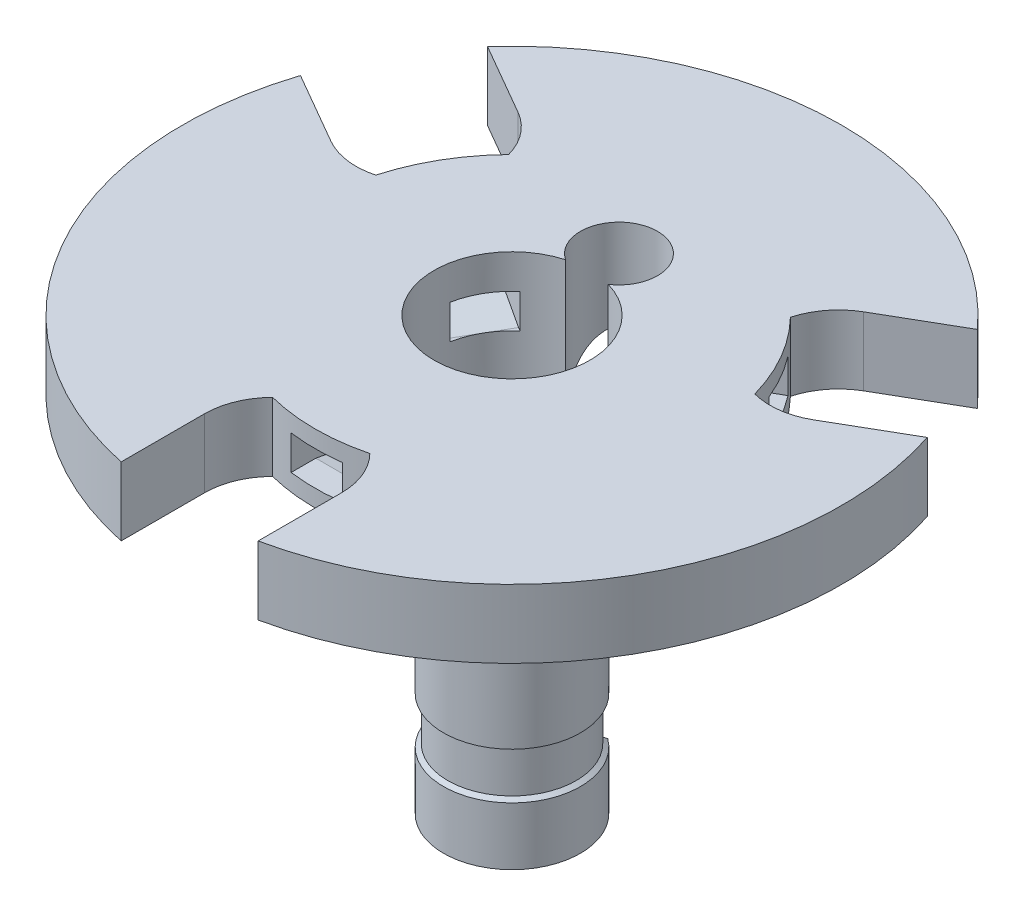
SolidWorks part; units mm, degrees
note: The reader was unsure of these and kept them because the rebuilt part matched: shared geometry of "Sketch1<4>".
ref_plane "Front Plane" through (0, 0, 0) normal (0, 0, 1) x (1, 0, 0)
ref_plane "Top Plane" through (0, 0, 0) normal (0, 1, 0) x (1, 0, 0)
ref_plane "Right Plane" through (0, 0, 0) normal (1, 0, 0) x (0, 0, -1)
sketch "Sketch1" plane through (0, 0, 0) normal (0, 1, 0) x (1, 0, 0)
  line L0 (-2, -16.5) -> (-2, -13.96)
  line L1 (2, -16.5) -> (2, -13.96)
  line L2 (0, -16.5) -> (0, 0) construction
  line L3 (0, 0) -> (38.1669, 22.0357) construction
  line L4 (0, 0) -> (-43.0695, 24.8662) construction
  line L5 (-11.0897, 8.7121) -> (-13.0897, 5.2479) construction
  line L6 (-13.2894, 9.9821) -> (-15.2894, 6.5179) construction
  line L7 (11.0897, 8.7121) -> (13.0897, 5.2479) construction
  line L8 (13.2894, 9.9821) -> (15.2894, 6.5179) construction
  line L9 (13.0897, 5.2479) -> (15.2894, 6.5179)
  line L10 (13.2894, 9.9821) -> (11.0897, 8.7121)
  line L11 (-15.2894, 6.5179) -> (-13.0897, 5.2479)
  line L12 (-13.2894, 9.9821) -> (-11.0897, 8.7121)
  line L13 (-4, -16.5) -> (-4, -13.96)
  line L14 (4, -16.5) -> (4, -13.96)
  line L15 (-16.2894, 4.7859) -> (-14.0897, 3.5159)
  line L16 (-12.2894, 11.7141) -> (-10.0897, 10.4441)
  line L17 (12.2894, 11.7141) -> (10.0897, 10.4441)
  line L18 (14.0897, 3.5159) -> (16.2894, 4.7859)
  line L19 (4, -16.5) -> (2.3, -16.5)
  line L20 (-4, -16.5) -> (-2.3, -16.5)
  line L21 (16.2894, 4.7859) -> (15.4394, 6.2581)
  line L22 (12.2894, 11.7141) -> (13.1394, 10.2419)
  line L23 (-12.2894, 11.7141) -> (-13.1394, 10.2419)
  line L24 (-16.2894, 4.7859) -> (-15.4394, 6.2581)
  line L25 (4, -16.5) -> (4, -18.8298)
  line L26 (-4, -16.5) -> (-4, -18.8298)
  line L27 (16.2894, 4.7859) -> (18.3071, 5.9508)
  line L28 (12.2894, 11.7141) -> (14.3071, 12.879)
  line L29 (-12.2894, 11.7141) -> (-14.3071, 12.879)
  line L30 (-16.2894, 4.7859) -> (-18.3071, 5.9508)
  circle A0 centre (0, 0) radius 16.5
  circle A1 centre (0, 0) radius 19.25
  arc A2 (-1.9963, -16.3788) -> (1.9963, -16.3788) centre (0, -16.5) ccw
  arc A3 (2, -13.96) -> (-2, -13.96) centre (0, -13.96) ccw
  circle A4 centre (0, 0) radius 4
  arc A5 (15.1826, 6.4605) -> (13.1863, 9.9183) centre (14.2894, 8.25) ccw
  arc A6 (-13.1863, 9.9183) -> (-15.1826, 6.4605) centre (-14.2894, 8.25) ccw
  arc A7 (-13.0897, 5.2479) -> (-11.095, 8.7151) centre (-12.0897, 6.98) ccw
  arc A8 (11.0897, 8.7121) -> (13.0897, 5.2479) centre (12.0897, 6.98) ccw
  arc A9 (4, -13.96) -> (-4, -13.96) centre (0, -13.96) ccw
  arc A10 (-14.0897, 3.5159) -> (-10.1003, 10.4502) centre (-12.0897, 6.98) ccw
  arc A11 (10.0897, 10.4441) -> (14.0897, 3.5159) centre (12.0897, 6.98) ccw
  arc A12 (-2.3, -16.5) -> (2.3, -16.5) centre (0, -16.5) ccw
  arc A13 (-2.2958, -16.3606) -> (2.2958, -16.3606) centre (0, -16.5) ccw construction
  arc A14 (-13.1394, 10.2419) -> (-15.4394, 6.2581) centre (-14.2894, 8.25) ccw
  arc A15 (15.4394, 6.2581) -> (13.1394, 10.2419) centre (14.2894, 8.25) ccw
  arc A16 (15.3166, 6.1921) -> (13.0208, 10.1685) centre (14.2894, 8.25) ccw construction
  arc A17 (-13.0208, 10.1685) -> (-15.3166, 6.1921) centre (-14.2894, 8.25) ccw construction
  circle A18 centre (0, 0) radius 11.5
  dimension "D1" = 38.5
  dimension "D2" = 33
  dimension "D3" = 4
  dimension "D5" = 8
  dimension "D8" = 4
  dimension "D9" = 4
  dimension "D10" = 4
  dimension "D11" = 4
  dimension "D20" = 23
  dimension "D4" = 2.54
  dimension "D6" = 120
  dimension "D7" = 120
  dimension "D12" = 2.54
  dimension "D13" = 2
  dimension "D14" = 2
  dimension "D15" = 2.54
  dimension "D16" = 2
  dimension "D17" = 2
  dimension "D18" = 0.3
  dimension "D19" = 0.3
extrude "Boss-Extrude1" add sketch "Sketch1" against normal blind 4 contours A1 A6 L12 A0 L10 A5 L9 L1 A2 L0 L11 | A11 L17 A0 L16 A10 L15 L13 A9 L14 L18 A4 | A18 A11 L17 A0 L16 A10 | A18 A9 L14 A0 L18 A11 | A18 A10 L15 A0 L13 A9 | A9 A18 | A10 A18 | A11 A18 | L30 A1 L26 L13 A0 L15 | L28 A1 L29 L16 A0 L17
extrude "Boss-Extrude2" add sketch "Sketch1<4>" against normal offset from surface (27.15 mm away) 27.15 contours A4 up to face at (0, 0, 0)
sketch "Sketch1<4>" plane through (0, 0, 0) normal (0, 1, 0) x (1, 0, 0) same geometry as "Sketch1"
sketch "Sketch2" plane through (0, 0, 0) normal (1, 0, 0) x (0, 0, -1)
  line L0 (0, 0) -> (0, -27.15) construction
  line L2 (2.3, -27.15) -> (2.3, -25.15)
  line L3 (2.5, 0) -> (2.3, -25.15)
  line L4 (-4, -27.15) -> (4, -27.15) construction
  line L6 (19.25, 0) -> (-19.25, 0) construction
  line L7 (0, 0) -> (2.5, 0)
  line L8 (0, -27.15) -> (2.3, -27.15)
  line L9 (0, 0) -> (0, -27.15)
  line L10 (0, -27.15) -> (2.3, -27.15)
  dimension "D1" = 2
  dimension "D2" = 2.5
  dimension "D3" = 2.3
revolve "Cut-Revolve4" cut sketch "Sketch2" angle 360 about L0
fillet "Fillet3" radius 10 1 edges at (0, -4, 4)
ref_axis "Axis1" through (0, 0, 0) along (0, -1, 0)
sketch "Sketch5" plane through (0, 0, 0) normal (0, 0, 1) x (1, 0, 0)
  line L0 (0, 0) -> (0, -7) construction
  line L1 (0, -7) -> (-2.55, -5.5278)
  line L2 (-2.55, -5.5278) -> (-2.55, 0)
  line L3 (-2.55, 0) -> (0, 0)
  line L4 (2.5, 0) -> (-2.5, 0) construction
  line L5 (0, 0) -> (0, -7) construction
  line L6 (0, 0) -> (0, -7)
  line L7 (-4.55, 0) -> (-4.55, -6.6825)
  line L8 (19.25, 0) -> (-19.25, 0) construction
  line L9 (-4.55, -6.6825) -> (0, -9.3094)
  line L10 (-4.55, 0) -> (-2.55, 0)
  line L11 (0, -7) -> (0, -9.3094)
  dimension "D1" = 7
  dimension "D2" = 60
  dimension "D3" = 2.55
  dimension "D4" = 5.5278
  dimension "D5" = 2
  dimension "D6" = 2
revolve "Cut-Revolve8" cut sketch "Sketch5" angle 360 about axis through (0, 0, 0) along (0, -1, 0)
sketch "Sketch6" plane through (0, -27.15, 0) normal (0, -1, 0) x (1, 0, 0)
  circle A0 centre (0, 0) radius 4
  circle A3 centre (0, 0) radius 4 construction
  arc A4 (3.356, 0) -> (3.356, 0) centre (0, 0) ccw
  circle A5 centre (0, 0) radius 3.356
  dimension "D1" = 0.644
extrude "Cut-Extrude1" cut sketch "Sketch6" against normal blind 1.932
ref_plane "Plane1" through (0, -23, 0) normal (0, 1, 0) x (1, 0, 0)
sketch "Sketch8" plane through (0, -23, 0) normal (0, 1, 0) x (1, 0, 0)
  line L0 (0, 0) -> (0, 6.5) construction
  circle A0 centre (0, 4) radius 2.5
  circle A1 centre (0, 0) radius 4 construction
  dimension "D1" = 5
extrude "Cut-Extrude3" cut sketch "Sketch8" along normal blind 5
chamfer "Chamfer1" distance 2 angle 20 1 edges at (0, -18, -4)
sketch "Sketch13" plane through (0, 0, 0) normal (1, 0, 0) x (0, 0, -1)
  line L0 (-4, -14) -> (-4, -25.218) construction
  line L1 (-4, -21.875) -> (-3.75, -21.875)
  line L2 (-4, -21.875) -> (-4, -19.125)
  line L3 (-4, -19.125) -> (-3.75, -19.125)
  line L4 (-3.75, -21.875) -> (-3.75, -19.125)
  point P6 (-4, -20.5)
  dimension "D1" = 2.75
  dimension "D2" = 0.25
  dimension "D3" = 2.5
sketch "Sketch7" plane through (0, -4, 0) normal (0, -1, 0) x (1, 0, 0)
  line L0 (0, 0) -> (0, -19.25) construction
  circle A0 centre (0, -6.25) radius 2.25
  circle A1 centre (0, 0) radius 4 construction
  circle A2 centre (0, 0) radius 19.25 construction
  dimension "D1" = 4.5
extrude "Cut-Extrude2" cut sketch "Sketch7" against normal through all and the other way through all
ref_axis "Axis2" through (0, -7.9023, 0) along (0, -1, 0)
revolve "Cut-Revolve14" cut sketch "Sketch13" angle 360 about axis through (0, -7.9023, 0) along (0, -1, 0)
chamfer "Chamfer4" distance 0.3 angle 35 1 edges at (0, -21.875, 3.75)
sketch "Sketch10" plane through (0, 0, 0) normal (1, 0, 0) x (0, 0, -1)
  line L0 (-9.96, -1) -> (-9.96, -3)
  line L1 (-4.55, -2) -> (-4.55, -4)
  line L3 (19.25, 0) -> (-19.25, 0) construction
  line L4 (-4.55, 0) -> (-4.55, -6.6825) construction
  line L5 (19.25, 0) -> (-19.25, 0) construction
  line L6 (-9.96, -1) -> (-9.96, -3)
  line L7 (-11.1432, -4) -> (3.1118, -4) construction
  line L8 (-11.1432, -4) -> (3.1118, -4) construction
  line L11 (-9.96, -1) -> (-4.55, -2)
  line L12 (-4.55, -4) -> (-9.96, -3)
  line L13 (-9.96, -1) -> (-12.96, -1)
  line L14 (-9.96, -1) -> (-9.96, -3)
  line L15 (-9.96, -3) -> (-12.96, -3)
  line L16 (-12.96, -1) -> (-12.96, -3)
  line L18 (-4.55, -2) -> (-1.55, -2)
  line L19 (-4.55, -2) -> (-4.55, -4)
  line L20 (-4.55, -4) -> (-1.55, -4)
  line L21 (-1.55, -2) -> (-1.55, -4)
  dimension "D1" = 2
  dimension "D2" = 1
  dimension "D3" = 3
  dimension "D4" = 1
  dimension "D5" = 3
  dimension "D6" = 5.41
extrude "Cut-Extrude15" cut sketch "Sketch10" against normal mid plane 3 contours L13 L16 L15 L0 | L12 L1 L11 L0 | L21 L18 L1 L20
pattern_circular "CirPattern2" count 3 every 120 about axis through (0, 0, 0) along (0, 1, 0) of "Cut-Extrude15"
sketch "Sketch14" plane through (0, -27.15, 0) normal (0, -1, 0) x (1, 0, 0)
  circle A0 centre (0, 0) radius 2.3 construction
  circle A1 centre (0, 0) radius 3.356 construction
  circle A2 centre (0, 0) radius 2.3
  circle A3 centre (0, 0) radius 3.356
extrude "Cut-Extrude16" cut sketch "Sketch14" against normal up to surface (1.932 mm away) up to face at (0, -25.218, -3.356)
sketch "Sketch15" plane through (0, 0, 0) normal (0, 1, 0) x (1, 0, 0)
  line L0 (0, 0) -> (-25.3486, 0) construction
  line L1 (0, 0) -> (0, -23.3308) construction
